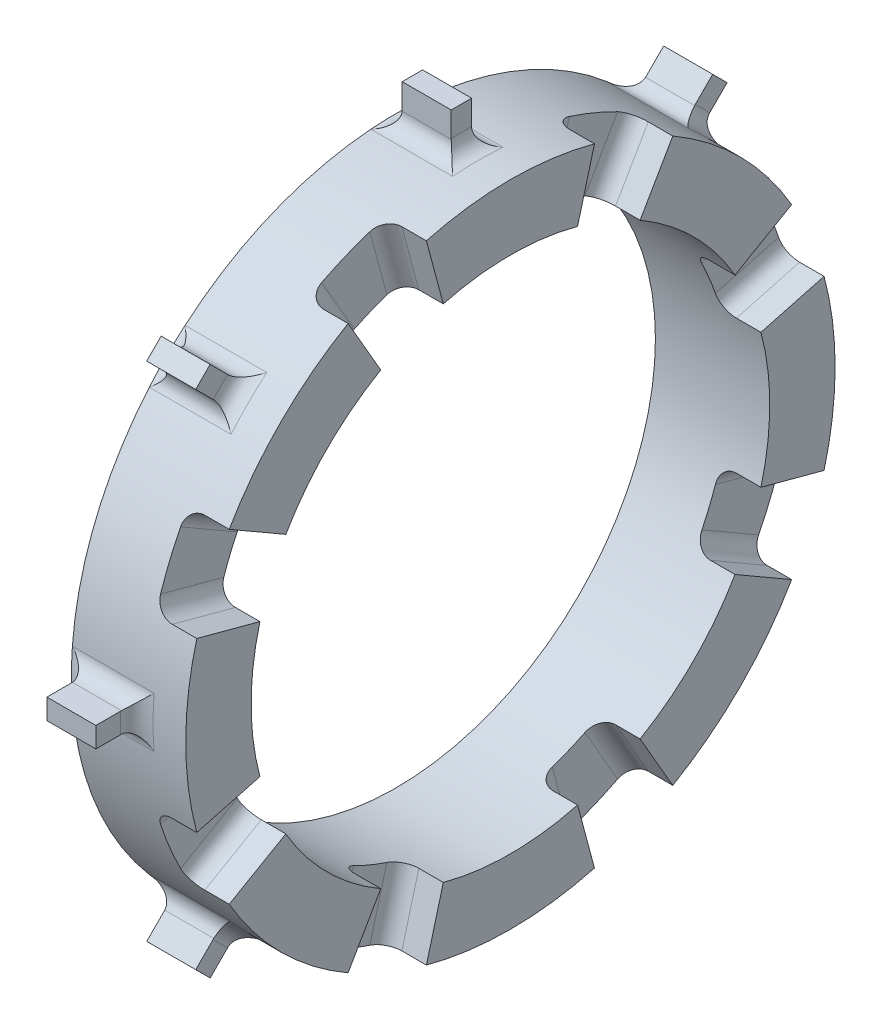
SolidWorks part; units mm, degrees
note: '?' marks a value the reader was unsure of.
material "7075-T6 (SN)"
ref_plane "Front Plane" through (0, 0, 0) normal (0, 0, 1) x (1, 0, 0)
ref_plane "Top Plane" through (0, 0, 0) normal (0, 1, 0) x (1, 0, 0)
ref_plane "Right Plane" through (0, 0, 0) normal (1, 0, 0) x (0, 0, -1)
ref_plane "Plane4" through (8, 0, 0) normal (1, 0, 0) x (0, 0, -1)
sketch "Sketch1" plane through (0, 0, 0) normal (1, 0, 0) x (0, 0, -1)
  circle A0 centre (0, 0) radius 31.75
  circle A1 centre (0, 0) radius 39.75
  dimension "D1" = 63.5
  dimension "D2" = 8
extrude "Boss-Extrude1" add sketch "Sketch1" along normal blind 14
sketch "Sketch2" plane through (8, 0, 0) normal (1, 0, 0) x (0, 0, -1)
  line L1 (39.7303, 1.25) -> (44.75, 1.25)
  line L3 (39.7303, -1.25) -> (44.75, -1.25)
  line L4 (44.75, 1.25) -> (44.75, -1.25)
  line L5 (39.75, 0) -> (44.75, -1.25) construction
  line L6 (39.75, 0) -> (44.75, 1.25) construction
  arc A1 (39.7303, -1.25) -> (39.7303, 1.25) centre (0, 0) ccw
  circle A2 centre (0, 0) radius 39.75
  circle A3 centre (0, 0) radius 39.75
  point P0 (39.75, 0)
  dimension "D1" = 0
  dimension "D2" = 2.5
  dimension "D3" = 5
extrude "Boss-Extrude2" add sketch "Sketch2" against normal blind 6 contours L1 L4 L3 A1
ref_axis "Axis1" through (14, 0, 0) along (-1, 0, 0)?
pattern_circular "CirPattern1" count 8 over 360 about axis through (0, 0, 0) along (1, 0, 0) of "Boss-Extrude2"
fillet "Fillet1" radius 2 32 edges at (5, 39.7303, 1.25) (5, 39.7303, -1.25) (5, 28.9775, 27.2097) (5, 27.2097, 28.9775) (5, -1.25, 39.7303) (5, 1.25, 39.7303) (5, -27.2097, 28.9775) (5, -28.9775, 27.2097) (5, -39.7303, -1.25) (5, -39.7303, 1.25) (5, -28.9775, -27.2097) (5, -1.25, -39.7303) (5, -27.2097, -28.9775) (5, 1.25, -39.7303) (5, 27.2097, -28.9775) (5, 28.9775, -27.2097) (2, 28.1075, -28.1075) (2, 39.75, 0) (2, 28.1075, 28.1075) (2, 0, 39.75) (2, -28.1075, 28.1075) (2, -39.75, 0) (2, -28.1075, -28.1075) (2, 0, -39.75) (8, 39.75, 0) (8, 28.1075, -28.1075) (8, 0, -39.75) (8, -28.1075, -28.1075) (8, -39.75, 0) (8, -28.1075, 28.1075) (8, 0, 39.75) (8, 28.1075, 28.1075)
ref_plane "Plane5" through (14, 0, 0) normal (1, 0, 0) x (0, 0, -1)
sketch "Sketch3" plane through (14, 0, 0) normal (1, 0, 0) x (0, 0, -1)
  line L0 (0, 0) -> (36.7242, -15.2117) construction
  line L1 (0, 0) -> (38.3956, -10.2881)
  line L2 (0, 0) -> (34.4245, -19.875)
  circle A0 centre (0, 0) radius 39.75 construction
  circle A1 centre (0, 0) radius 39.75
  point P39 (0, 0)
extrude "Cut-Extrude2" cut sketch "Sketch3" against normal blind 5 contours L0 L2 A1 | L1 L0 A1
fillet "Fillet2" radius 2 2 edges at (9, -17.875, -30.9604) (9, -9.2528, -34.5318)
pattern_circular "CirPattern2" count 8 every 45 about axis through (0, 0, 0) along (1, 0, 0) of "Cut-Extrude2", "Fillet2"
thread "Thread1" [suppressed] pitch 1.5 start angle 0, offset 2, length 20, pitch 1.5, diameter 63.5
ref_plane "Plane3" through (-2, 0, -31.75) normal (0, -1, 0) x (0, 0, -1)
sketch "Thread Profile2" plane through (-2, 0, -31.75) normal (0, -1, 0) x (0, 0, -1)
  line L0 (0, 0) -> (0, 1.5) construction
  line L1 (0, 0) -> (0.8119, 0.4687)
  line L2 (0.8119, 0.4687) -> (0.8119, 0.6562)
  line L3 (0.8119, 0.6562) -> (0, 1.125)
  line L4 (0.8119, 0.5625) -> (0, 0.5625) construction
  line L11 (0, 0) -> (0, 1.125)
  point P2 (0, 0)
  dimension "Pitch" = 1.5
  dimension "Profile_Angle" = 60
  dimension "Profile_Land" = 0.1875
  dimension "Profile_Height" = 0.8119
equation "\"mm\"=2"
